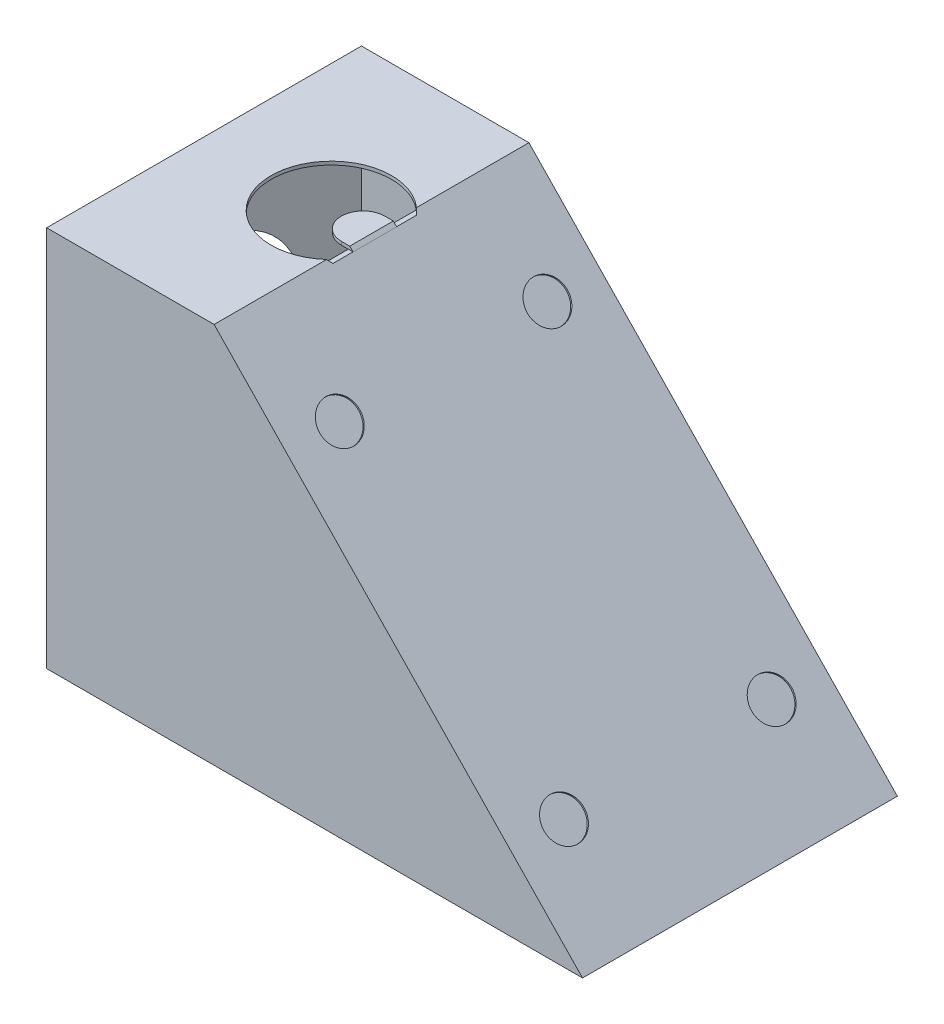
SolidWorks part; units mm, degrees
material "Nickel"
ref_plane "Front Plane" through (0, 0, 0) normal (0, 0, 1) x (1, 0, 0)
ref_plane "Top Plane" through (0, 0, 0) normal (0, 1, 0) x (1, 0, 0)
ref_plane "Right Plane" through (0, 0, 0) normal (1, 0, 0) x (0, 0, -1)
sketch "Sketch1" plane through (0, 0, 0) normal (0, 0, 1) x (1, 0, 0)
  line L0 (0, 0) -> (40.64, 0)
  line L1 (0, 0) -> (0, 28.956)
  line L2 (0, 28.956) -> (12.7, 28.956)
  line L3 (12.7, 28.956) -> (40.64, 0)
  dimension "D1" = 40.64
  dimension "D2" = 28.956
  dimension "D3" = 12.7
extrude "Boss-Extrude1" add sketch "Sketch1" against normal blind 23.876
shell "Shell1" thickness 0.254 removed face at (20.32, 0, -11.938)
sketch "Sketch2" plane through (0, 0, 0) normal (-1, 0, 0) x (0, 0, 1)
  line L0 (-23.876, 0) -> (0, 0) construction
  line L1 (-23.876, 28.956) -> (0, 28.956) construction
  line L2 (0, 28.956) -> (0, 0) construction
  circle A0 centre (-11.938, 14.859) radius 7.239
  point P9 (-11.938, 28.956)
  dimension "D1" = 14.478
  dimension "D2" = 14.859
  dimension "D3" = 11.938
extrude "Cut-Extrude1" cut sketch "Sketch2" against normal blind 0.254
chamfer "Chamfer1" distance 0.254 angle 45 1 edges at (0, 14.859, -4.699)
sketch "Sketch3" plane through (21.0455, 20.307, 0) normal (0.7196, 0.6944, 0) x (0, 0, -1)
  line L0 (23.876, -28.2192) -> (23.876, 12.0188) construction
  line L1 (23.876, 12.0188) -> (0, 12.0188) construction
  line L2 (23.876, -28.2192) -> (0, -28.2192) construction
  line L3 (0, -28.2192) -> (0, 12.0188) construction
  circle A0 centre (19.812, 4.1448) radius 1.524
  circle A1 centre (19.812, -20.3452) radius 1.524
  circle A2 centre (4.064, 4.1448) radius 1.524
  circle A3 centre (4.064, -20.3452) radius 1.524
  dimension "D1" = 3.048
  dimension "D4" = 3.048
  dimension "D7" = 4.064
  dimension "D2" = 4.064
  dimension "D3" = 7.874
  dimension "D5" = 7.874
  dimension "D6" = 4.064
extrude "Cut-Extrude2" cut sketch "Sketch3" against normal blind 0.127
sketch "Sketch9" plane through (0, 28.956, 0) normal (0, 1, 0) x (1, 0, 0)
  line L0 (12.7, 23.876) -> (12.7, 0) construction
  line L1 (5.08, 18.4339) -> (5.08, 6.691) construction
  circle A0 centre (9.652, 11.938) radius 4.572
  point P8 (12.7, 11.938)
  dimension "D1" = 9.144
  dimension "D2" = 7.62
extrude "Cut-Extrude3" cut sketch "Sketch9" against normal blind 0.254 contours A0
ref_plane "Plane4" through (0, 0, -11.938) normal (0, 0, 1) x (1, 0, 0)
sketch "Sketch18" plane through (0, 0, -11.938) normal (0, 0, 1) x (1, 0, 0)
  line L0 (12.7, 28.956) -> (10.414, 28.956)
  line L1 (12.7, 28.956) -> (0, 28.956) construction
  line L2 (10.414, 28.956) -> (10.414, 28.702)
  line L3 (10.414, 28.702) -> (12.7, 28.702)
  line L4 (12.7, 28.702) -> (12.7, 28.956)
  dimension "D1" = 2.286
  dimension "D2" = 0.254
extrude "Boss-Extrude5" add sketch "Sketch18" along normal mid plane 3.302
sketch "Sketch19" plane through (0, 28.956, 0) normal (0, 1, 0) x (1, 0, 0)
  line L0 (10.414, 10.287) -> (10.414, 13.589) construction
  line L1 (12.7, 10.287) -> (10.414, 10.287) construction
  line L2 (12.065, 10.287) -> (10.414, 10.287)
  line L3 (10.414, 10.287) -> (10.414, 13.6581)
  line L4 (10.414, 13.6581) -> (12.065, 13.589)
  circle A0 centre (12.065, 11.938) radius 1.651
  line M2 (12.7, 13.589) -> (10.414, 13.589)
  line M3 (10.414, 13.589) -> (10.414, 10.287)
  line M4 (10.414, 10.287) -> (12.7, 10.287)
  dimension "D1" = 3.302
extrude "Cut-Extrude4" cut sketch "Sketch19" against normal blind 3.302 contours A0 L3 M4 | A0 M2 M3 region at (10.7828, 28.956, -10.6558) region at (10.7828, 28.956, -13.2202)
sketch "Sketch20" plane through (12.7, 0, 0) normal (1, 0, 0) x (0, 0, -1)
  line L1 (10.287, 28.956) -> (13.589, 28.956)
  line L2 (10.287, 28.956) -> (10.287, 28.702)
  line L3 (10.287, 28.702) -> (13.589, 28.702)
  line L4 (13.589, 28.956) -> (13.589, 28.702)
extrude "Boss-Extrude6" add sketch "Sketch20" along normal blind 0.254
sketch "Sketch22" plane through (0, 0, -11.938) normal (0, 0, 1) x (1, 0, 0)
  line L0 (12.7, 28.956) -> (12.954, 28.702)
  line L1 (12.954, 28.702) -> (12.954, 28.956)
  line L2 (12.954, 28.956) -> (12.7, 28.956)
extrude "Cut-Extrude5" cut sketch "Sketch22" against normal mid plane 5.334
sketch "Sketch23" plane through (0, 0, 0) normal (0, -1, 0) x (1, 0, 0)
  line L0 (40.287, -13.589) -> (39.652, -13.589)
  line L1 (40.287, -23.622) -> (40.287, -0.254) construction
  line L2 (40.287, -10.287) -> (40.287, -0.254)
  line L3 (39.652, -10.287) -> (40.287, -10.287)
  line L4 (40.287, -0.254) -> (40.287, -23.622) construction
  line L5 (40.287, -10.287) -> (40.287, -13.589)
  line L8 (0.254, -0.254) -> (0.254, -23.622)
  line L9 (40.287, -0.254) -> (0.254, -0.254)
  line L10 (40.287, -23.622) -> (40.287, -0.254)
  line L11 (0.254, -23.622) -> (40.287, -23.622)
  line L12 (0.254, -0.254) -> (0.254, -23.622)
  line L13 (40.287, -0.254) -> (0.254, -0.254)
  line L14 (40.287, -23.622) -> (40.287, -13.589)
  line L15 (0.254, -23.622) -> (40.287, -23.622)
  arc A0 (39.652, -10.287) -> (39.652, -13.589) centre (39.652, -11.938) ccw
  point P10 (40.287, -11.938)
  line M16 (40.287, -0.254) -> (40.287, -23.622)
  dimension "D3" = 3.302
  dimension "D1" = 0
extrude "Boss-Extrude7" add sketch "Sketch23" against normal blind 0.254 contours L3 A0 L0 M16 region at (39.286, 0, -11.938)
